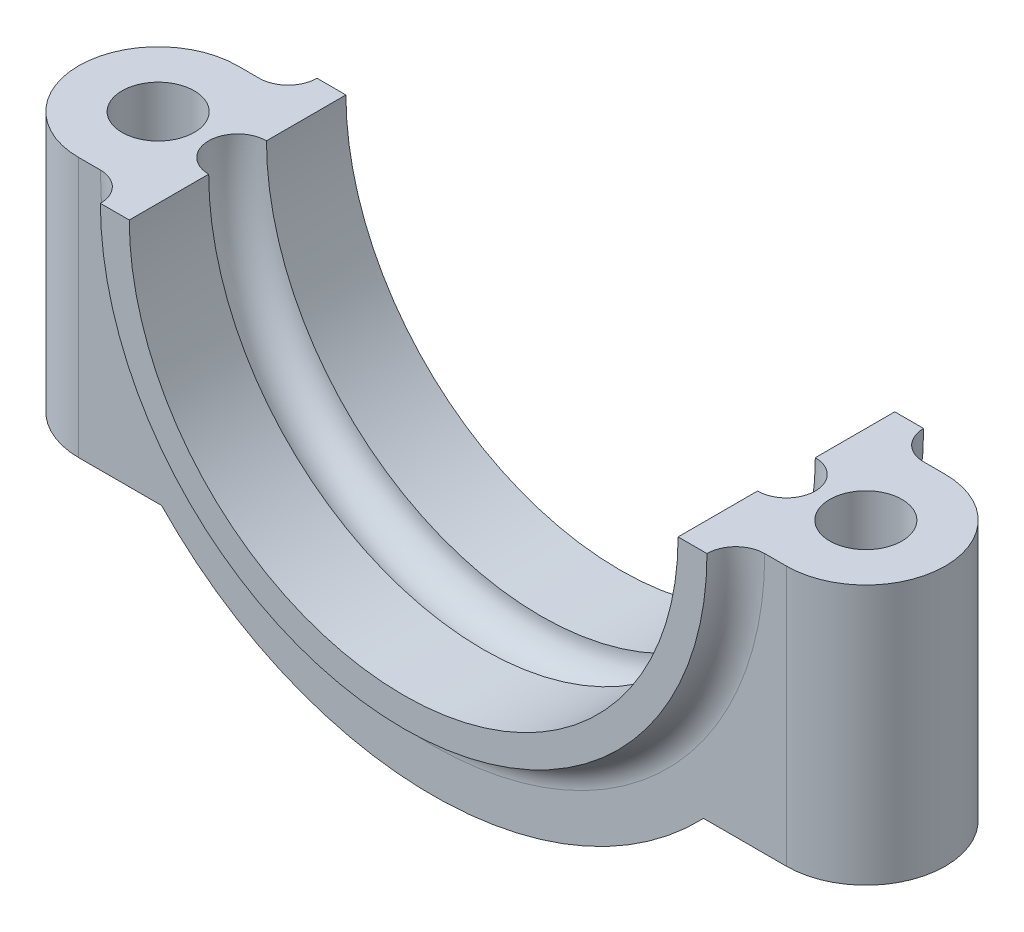
SolidWorks part; units mm, degrees
material "Teak"
ref_plane "Plano frontal" through (0, 0, 0) normal (0, 0, 1) x (1, 0, 0)
ref_plane "Plano superior" through (0, 0, 0) normal (0, 1, 0) x (1, 0, 0)
ref_plane "Plano direito" through (0, 0, 0) normal (1, 0, 0) x (0, 0, -1)
sketch "Sketch1" plane through (0, 0, 0) normal (0, 0, 1) x (1, 0, 0)
  line L0 (19, 0) -> (30, 0)
  line L1 (30, 0) -> (30, -18)
  line L2 (30, -18) -> (18.7617, -18)
  line L3 (-19, 0) -> (-30, 0)
  line L4 (-30, 0) -> (-30, -18)
  line L5 (-30, -18) -> (-18.7617, -18)
  arc A0 (-19, 0) -> (19, 0) centre (0, 0) ccw
  arc A1 (-18.7617, -18) -> (18.7617, -18) centre (0, 0) ccw
  dimension "D1" = 38
  dimension "D2" = 52
  dimension "D3" = 60
  dimension "D4" = 18
extrude "Boss-Extrude1" add sketch "Sketch1" along normal mid plane 11
sketch "Sketch2" plane through (0, 0, -5.5) normal (0, 0, -1) x (-1, 0, 0)
  line L0 (-21, 0) -> (-19, 0)
  line L1 (19, 0) -> (21, 0)
  arc A0 (-21, 0) -> (21, 0) centre (0, 0) ccw
  arc A1 (-19, 0) -> (19, 0) centre (0, 0) ccw construction
  arc A2 (-19, 0) -> (19, 0) centre (0, 0) ccw
  dimension "D1" = 42
extrude "Boss-Extrude2" add sketch "Sketch2" along normal blind 2 and the other way blind 13
sketch "Sketch3" plane through (0, 0, 0) normal (0, 1, 0) x (1, 0, 0)
  line L0 (0, 0) -> (0, 16.2974) construction
  circle A0 centre (-24.5, 0) radius 2.5
  circle A1 centre (24.5, 0) radius 2.5
  dimension "D1" = 5
extrude "Cut-Extrude1" cut sketch "Sketch3" against normal through all
sketch "Sketch4" plane through (0, 0, 0) normal (0, 1, 0) x (1, 0, 0)
  line L0 (-19, -7.5) -> (-19, 7.5) construction
  line L1 (0, 0) -> (0, 16.9066) construction
  circle A0 centre (-19, 0) radius 2
  dimension "D1" = 4
revolve "Cut-Revolve1" cut sketch "Sketch4" angle 360 about L1
fillet "Fillet1" radius 2 2 edges at (0, -21, -5.5) (0, -21, 5.5)
fillet "Fillet2" 2 edges at (-30, -9, 5.5) (-30, -9, -5.5) type full round first side face at (0, -12.875, 5.5) second side face at (0, -12.875, -5.5) middle face at (-30, -9, 0)
fillet "Fillet3" 2 edges at (30, -9, -5.5) (30, -9, 5.5) type full round first side face at (1.375, -12.875, -5.5) second side face at (1.375, -12.875, 5.5) middle face at (30, -9, 0)
